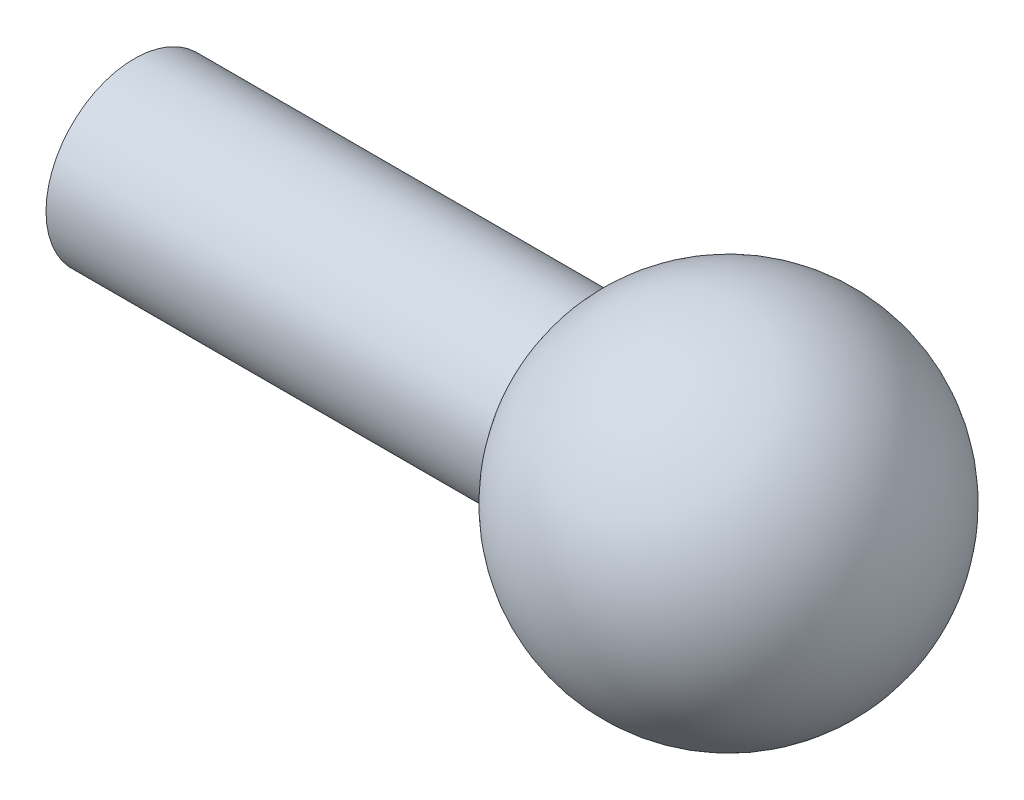
SolidWorks part; units mm, degrees
material "PLA"
ref_plane "Front Plane" through (0, 0, 0) normal (0, 0, 1) x (1, 0, 0)
ref_plane "Top Plane" through (0, 0, 0) normal (0, 1, 0) x (1, 0, 0)
ref_plane "Right Plane" through (0, 0, 0) normal (1, 0, 0) x (0, 0, -1)
sketch "Sketch1" plane through (0, 0, 0) normal (0, 1, 0) x (1, 0, 0)
  line L0 (-6.35, 0) -> (15.8294, 0)
  line L1 (6.35, 2.54) -> (-6.35, 2.54)
  line L4 (-6.35, 2.54) -> (-6.35, 0)
  line L5 (6.35, 2.54) -> (0, 0) construction
  line L6 (0, 0) -> (-6.35, 2.54) construction
  arc A1 (6.35, 2.54) -> (15.8294, 0) centre (10.7494, 0) cw
  point P0 (0, 0)
  dimension "D3" = 5.08
  dimension "D1" = 2.54
  dimension "D2" = 12.7
  dimension "D4" = 6.35
revolve "Revolve1" add sketch "Sketch1" angle 360 about L0
ref_plane "Plane1" through (15.8294, 0, 0) normal (1, 0, 0) x (0, 0, -1)
sketch "Sketch2" plane through (15.8294, 0, 0) normal (1, 0, 0) x (0, 0, -1)
  point P0 (0, 0)
